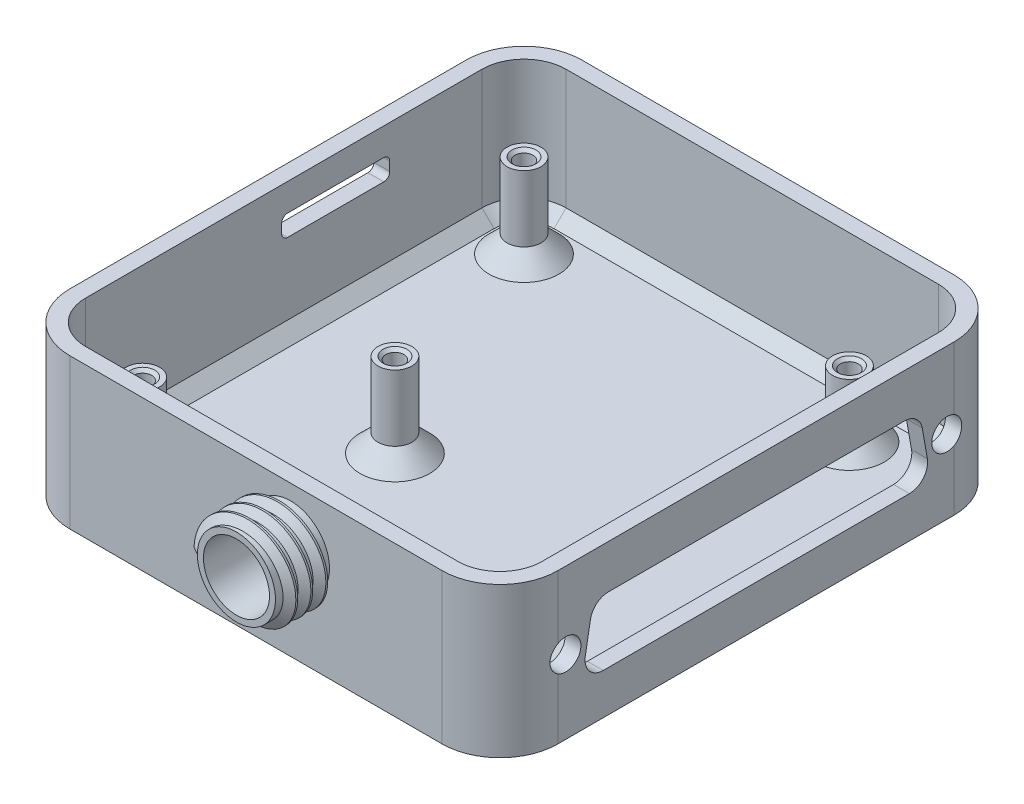
SolidWorks part; units mm, degrees
ref_plane "Front Plane" through (0, 0, 0) normal (0, 0, 1) x (1, 0, 0)
ref_plane "Top Plane" through (0, 0, 0) normal (0, 1, 0) x (1, 0, 0)
ref_plane "Right Plane" through (0, 0, 0) normal (1, 0, 0) x (0, 0, -1)
sketch "HRDAQ_PCB_Sketch" plane through (0, 0, 0) normal (0, 1, 0) x (1, 0, 0)
  line L0 (4, -38.85) -> (13, -38.85)
  line L1 (-27.1, -31.75) -> (27.1, -31.75) construction
  line L2 (-27.1, -31.75) -> (-27.1, 31.75) construction
  line L3 (-27.1, 31.75) -> (27.1, 31.75) construction
  line L4 (27.1, -31.75) -> (27.1, 31.75) construction
  line L5 (-27.1, -31.75) -> (27.1, 31.75) construction
  line L6 (-27.1, 31.75) -> (27.1, -31.75) construction
  line L7 (-28.25, 35.9) -> (33.75, 35.9)
  line L8 (-31.25, 32.9) -> (-31.25, -33.1)
  line L9 (-28.25, -36.1) -> (1.25, -36.1)
  line L10 (36.75, 32.9) -> (36.75, -33.1)
  line L11 (4, -38.85) -> (1.25, -36.1)
  line L12 (13, -38.85) -> (15.75, -36.1)
  line L13 (15.75, -36.1) -> (33.75, -36.1)
  circle A0 centre (-27.1, 31.75) radius 1.5
  circle A1 centre (27.1, 31.75) radius 1.5
  circle A2 centre (27.1, -31.75) radius 1.5
  circle A3 centre (-27.1, -31.75) radius 1.5
  circle A4 centre (-9.1, -7.75) radius 1.5
  arc A5 (-28.25, -36.1) -> (-31.25, -33.1) centre (-28.25, -33.1) cw
  arc A6 (33.75, -36.1) -> (36.75, -33.1) centre (33.75, -33.1) ccw
  arc A7 (36.75, 32.9) -> (33.75, 35.9) centre (33.75, 32.9) ccw
  arc A8 (-28.25, 35.9) -> (-31.25, 32.9) centre (-28.25, 32.9) ccw
  point P0 (0, 0)
  point P12 (8.5, -38.85)
  point P20 (8.5, -38.85)
  point P26 (36.75, -36.1)
  point P29 (36.75, 35.9)
  point P32 (-31.25, 35.9)
  dimension "D3" = 3
  dimension "D14" = 3
  dimension "D1" = 54.2
  dimension "D2" = 63.5
  dimension "D4" = 24
  dimension "D5" = 18
  dimension "D6" = 35.6
  dimension "D7" = 7.1
  dimension "D8" = 4.15
  dimension "D9" = 9
  dimension "D10" = 4.15
  dimension "D11" = 72
  dimension "D12" = 68
  dimension "D13" = 135
sketch "HRDAQ_PCB_Base_Sketch" plane through (0, 0, 0) normal (0, 1, 0) x (1, 0, 0)
  line L8 (-28.25, -40.1) -> (33.75, -40.1)
  line L9 (-37.89, 32.9) -> (-37.89, -33.1)
  line L10 (-28.25, -42.74) -> (33.75, -42.74)
  line L11 (43.39, -33.1) -> (43.39, 32.9)
  line L12 (33.75, 42.54) -> (-28.25, 42.54)
  line L16 (-35.25, 32.9) -> (-35.25, -33.1)
  line L17 (-28.25, -40.1) -> (-0.4069, -40.1)
  line L18 (-0.4069, -40.1) -> (2.3431, -42.85)
  line L19 (2.3431, -42.85) -> (14.6569, -42.85)
  line L20 (14.6569, -42.85) -> (17.4069, -40.1)
  line L21 (17.4069, -40.1) -> (33.75, -40.1)
  line L22 (40.75, -33.1) -> (40.75, 32.9)
  line L23 (33.75, 39.9) -> (-28.25, 39.9)
  line L24 (-35.25, 32.9) -> (-35.25, -33.1)
  line L30 (40.75, -33.1) -> (40.75, 32.9)
  line L31 (33.75, 39.9) -> (-28.25, 39.9)
  arc A4 (-37.89, -33.1) -> (-28.25, -42.74) centre (-28.25, -33.1) ccw
  arc A5 (33.75, -42.74) -> (43.39, -33.1) centre (33.75, -33.1) ccw
  arc A6 (43.39, 32.9) -> (33.75, 42.54) centre (33.75, 32.9) ccw
  arc A7 (-28.25, 42.54) -> (-37.89, 32.9) centre (-28.25, 32.9) ccw
  arc A8 (-35.25, -33.1) -> (-28.25, -40.1) centre (-28.25, -33.1) ccw
  arc A9 (33.75, -40.1) -> (40.75, -33.1) centre (33.75, -33.1) ccw
  arc A10 (40.75, 32.9) -> (33.75, 39.9) centre (33.75, 32.9) ccw
  arc A11 (-28.25, 39.9) -> (-35.25, 32.9) centre (-28.25, 32.9) ccw
  arc A12 (-35.25, -33.1) -> (-28.25, -40.1) centre (-28.25, -33.1) ccw
  arc A13 (33.75, -40.1) -> (40.75, -33.1) centre (33.75, -33.1) ccw
  arc A14 (40.75, 32.9) -> (33.75, 39.9) centre (33.75, 32.9) ccw
  arc A15 (-28.25, 39.9) -> (-35.25, 32.9) centre (-28.25, 32.9) ccw
  dimension "D1" = 4
  dimension "D2" = 2.64
sketch "Sketch1" plane through (0, 0, 0) normal (0, 1, 0) x (1, 0, 0)
  line L0 (-28.25, -42.74) -> (33.75, -42.74) construction
  line L1 (43.39, -33.1) -> (43.39, 32.9) construction
  line L2 (33.75, 42.54) -> (-28.25, 42.54) construction
  line L3 (-37.89, 32.9) -> (-37.89, -33.1) construction
  line L4 (-28.25, -42.74) -> (33.75, -42.74)
  line L5 (43.39, -33.1) -> (43.39, 32.9)
  line L6 (33.75, 42.54) -> (-28.25, 42.54)
  line L7 (-37.89, 32.9) -> (-37.89, -33.1)
  arc A0 (-37.89, -33.1) -> (-28.25, -42.74) centre (-28.25, -33.1) ccw construction
  arc A1 (33.75, -42.74) -> (43.39, -33.1) centre (33.75, -33.1) ccw construction
  arc A2 (43.39, 32.9) -> (33.75, 42.54) centre (33.75, 32.9) ccw construction
  arc A3 (-28.25, 42.54) -> (-37.89, 32.9) centre (-28.25, 32.9) ccw construction
  arc A4 (-37.89, -33.1) -> (-28.25, -42.74) centre (-28.25, -33.1) ccw
  arc A5 (33.75, -42.74) -> (43.39, -33.1) centre (33.75, -33.1) ccw
  arc A6 (43.39, 32.9) -> (33.75, 42.54) centre (33.75, 32.9) ccw
  arc A7 (-28.25, 42.54) -> (-37.89, 32.9) centre (-28.25, 32.9) ccw
  circle A8 centre (27.1, -31.75) radius 1.5 construction
  circle A9 centre (-27.1, -31.75) radius 1.5 construction
  circle A10 centre (-9.1, -7.75) radius 1.5 construction
  circle A11 centre (27.1, 31.75) radius 1.5 construction
  circle A12 centre (-27.1, 31.75) radius 1.5 construction
  circle A13 centre (27.1, -31.75) radius 1.5
  circle A14 centre (-27.1, -31.75) radius 1.5
  circle A15 centre (-9.1, -7.75) radius 1.5
  circle A16 centre (27.1, 31.75) radius 1.5
  circle A17 centre (-27.1, 31.75) radius 1.5
extrude "Base_Extrude" add sketch "Sketch1" along normal blind 3
extrude "Wall_Extrude" add sketch "HRDAQ_PCB_Base_Sketch" along normal blind 25
chamfer "Base_Chamfer" distance 2 angle 45 8 edges at (2.75, 3, 40.1) (-33.1997, 3, 38.0497) (38.6997, 3, 38.0497) (-35.25, 3, 0.1) (40.75, 3, 0.1) (-33.1997, 3, -37.8497) (38.6997, 3, -37.8497) (2.75, 3, -39.9)
sketch "Sketch2" plane through (0, 3, 0) normal (0, 1, 0) x (1, 0, 0)
  circle A0 centre (-27.1, 31.75) radius 2.82
  circle A1 centre (-9.1, -7.75) radius 2.82
  circle A2 centre (-27.1, -31.75) radius 2.82
  circle A3 centre (-27.1, 31.75) radius 1.5
  circle A4 centre (-9.1, -7.75) radius 1.5
  circle A5 centre (-27.1, -31.75) radius 1.5
  circle A7 centre (-27.1, 31.75) radius 1.5 construction
  dimension "D1" = 5.64
extrude "Small_Peg_Extrude" add sketch "Sketch2" along normal blind 14
sketch "Sketch3" plane through (0, 3, 0) normal (0, 1, 0) x (1, 0, 0)
  circle A0 centre (27.1, 31.75) radius 2.82
  circle A1 centre (27.1, -31.75) radius 2.82
  circle A2 centre (27.1, 31.75) radius 1.5
  circle A3 centre (27.1, -31.75) radius 1.5
  circle A4 centre (27.1, 31.75) radius 1.5 construction
  dimension "D1" = 5.64
extrude "DSUB_Peg_Extrude" add sketch "Sketch3" along normal blind 11
chamfer "Peg_Chamfer_1" distance 3 angle 45 5 edges at (27.1, 3, 34.57) (-27.1, 3, 34.57) (-9.1, 3, 10.57) (27.1, 3, -28.93) (-27.1, 3, -28.93)
chamfer "Peg_Chamfer_2" distance 0.5 angle 45 5 edges at (27.1, 14, 33.25) (-27.1, 17, 33.25) (-9.1, 17, 9.25) (27.1, 14, -30.25) (-27.1, 17, -30.25)
ref_plane "HRDAQ_PCB_Top_Plane" through (0, 18.55, 0) normal (0, 1, 0) x (1, 0, 0)
sketch "Sketch4" plane through (0, 0, 42.74) normal (0, 0, 1) x (1, 0, 0)
  line L0 (8.5, 0) -> (8.5, 25) construction
  line L1 (-28.25, 25) -> (33.75, 25) construction
  line L2 (50.856, 18.55) -> (-50.856, 18.55) construction
  circle A0 centre (8.5, 15.95) radius 2.6 construction
  circle A1 centre (8.5, 15.95) radius 5.5
  point P0 (8.5, 0)
  dimension "D1" = 5.2
  dimension "D2" = 11
extrude "SMA_Cut_Extrude" cut sketch "Sketch4" against normal up to surface (2.64 mm away) up to face at (2.75, 15, 40.1)
sketch "Sketch5" plane through (43.39, 0, 0) normal (1, 0, 0) x (0, 0, -1)
  line L0 (0, 0) -> (-0.1, 25) construction
  line L1 (-33.1, 25) -> (32.9, 25) construction
  line L2 (50.856, 18.55) -> (-50.856, 18.55) construction
  line L3 (-34.7074, 6.0024) -> (34.6092, 6.0024)
  line L4 (-34.7074, 6.0024) -> (-34.7074, 18.55)
  line L5 (-34.7074, 18.55) -> (34.6092, 18.55)
  line L6 (34.6092, 6.0024) -> (34.6092, 18.55)
  line L7 (-34.7074, 6.0024) -> (34.6092, 18.55) construction
  line L8 (-34.7074, 18.55) -> (34.6092, 6.0024) construction
  line L9 (-34.7074, 12.2762) -> (34.6092, 12.2762) construction
  line L10 (-25.5468, 7.8265) -> (25.4499, 7.8265)
  line L12 (-26.3992, 16.7259) -> (26.3062, 16.7259)
  line L14 (-27.9684, 7.8265) -> (27.8702, 16.7259) construction
  line L15 (-27.9684, 16.7259) -> (27.8702, 7.8265) construction
  line L16 (-31.7991, 12.2762) -> (31.7009, 12.2762) construction
  line L17 (-27.5479, 10.2114) -> (-26.6953, 15.0468)
  line L18 (27.4513, 10.2102) -> (26.6015, 15.0456)
  line L19 (-27.9684, 7.8265) -> (27.8702, 7.8265)
  line L20 (-24.6942, 16.7259) -> (24.6001, 16.7259)
  line L21 (-26.3992, 16.7259) -> (-27.9684, 16.7259)
  line L22 (-27.9684, 16.7259) -> (-27.9684, 7.8265)
  line L23 (27.8702, 7.8265) -> (27.8702, 16.7259)
  line L24 (27.8702, 16.7259) -> (26.3062, 16.7259)
  circle A2 centre (-31.7991, 12.2762) radius 2.54
  circle A3 centre (31.7009, 12.2762) radius 2.54
  arc A4 (25.4499, 7.8265) -> (27.4513, 10.2102) centre (25.4499, 9.8585) ccw
  arc A5 (26.6015, 15.0456) -> (24.6001, 16.7259) centre (24.6001, 14.6939) ccw
  arc A6 (-26.6953, 15.0468) -> (-24.6942, 16.7259) centre (-24.6942, 14.6939) cw
  arc A7 (-25.5468, 7.8265) -> (-27.5479, 10.2114) centre (-25.5468, 9.8585) cw
  point P5 (-0.0491, 12.2762)
  point P12 (-0.0491, 12.2762)
  point P23 (-0.0491, 12.2762)
  line M3 (32.9, 0) -> (32.9, 25)
  line M5 (-33.1, 25) -> (-33.1, 0)
  dimension "D6" = 63.5
  dimension "D5" = 5.08
  dimension "D7" = 2.032
  dimension "D1" = 69.3166
  dimension "D2" = 12.5476
  dimension "D3" = 55.8386
  dimension "D4" = 8.8994
extrude "DSUB_Cut_Extrude" cut sketch "Sketch5" against normal up to vertex (9.64 mm away) contours A7 L10 A4 L18 A5 L12 A6 L17 | A2 M5 | A2 M5 | A3 M3 | A3 M3 region at (43.39, 12.2762, 31.3781) region at (43.39, 12.2762, 33.6077) region at (43.39, 12.2762, -33.4507) region at (43.39, 12.2762, -31.2329) region at (43.39, 12.2446, 0.0478) up to point (33.75, 25, -39.9)
sketch "Sketch6" plane through (-37.89, 0, 0) normal (-1, 0, 0) x (0, 0, 1)
  line L0 (50.856, 18.55) -> (-50.856, 18.55) construction
  line L1 (-16.54, 20.43) -> (-0.54, 20.43)
  line L2 (-17.54, 19.43) -> (-17.54, 17.93)
  line L3 (-16.54, 16.93) -> (-0.54, 16.93)
  line L4 (0.46, 19.43) -> (0.46, 17.93)
  line L5 (-42.54, 25) -> (-42.54, 0) construction
  arc A0 (-17.54, 17.93) -> (-16.54, 16.93) centre (-16.54, 17.93) ccw
  arc A1 (-0.54, 16.93) -> (0.46, 17.93) centre (-0.54, 17.93) ccw
  arc A2 (-0.54, 20.43) -> (0.46, 19.43) centre (-0.54, 19.43) cw
  arc A3 (-16.54, 20.43) -> (-17.54, 19.43) centre (-16.54, 19.43) ccw
  point P10 (-17.54, 16.93)
  point P13 (0.46, 16.93)
  point P16 (0.46, 20.43)
  point P19 (-17.54, 20.43)
  dimension "D5" = 1
  dimension "D1" = 1.62
  dimension "D2" = 3.5
  dimension "D3" = 18
  dimension "D4" = 25
extrude "SD-Card_Cut_Extrude" cut sketch "Sketch6" against normal up to surface (2.64 mm away) up to face at (-35.25, 15, 0.1)
sketch "Sketch7" plane through (43.39, 0, 0) normal (1, 0, 0) x (0, 0, -1)
  line L0 (-27.5479, 10.2114) -> (-26.6953, 15.0468) construction
  line L1 (-25.5468, 7.8265) -> (25.4499, 7.8265) construction
  line L2 (27.4513, 10.2102) -> (26.6015, 15.0456) construction
  line L3 (-24.6942, 16.7259) -> (24.6001, 16.7259) construction
  line L4 (-27.5479, 10.2114) -> (-26.6953, 15.0468)
  line L5 (-25.5468, 7.8265) -> (25.4499, 7.8265)
  line L6 (27.4513, 10.2102) -> (26.6015, 15.0456)
  line L7 (-24.6942, 16.7259) -> (24.6001, 16.7259)
  line L8 (-24.6942, 17.7259) -> (24.6001, 17.7259)
  line L9 (28.4362, 10.3833) -> (27.5864, 15.2187)
  line L10 (-25.5468, 6.8265) -> (25.4499, 6.8265)
  line L11 (-28.5327, 10.385) -> (-27.6801, 15.2204)
  arc A0 (-24.6942, 16.7259) -> (-26.6953, 15.0468) centre (-24.6942, 14.6939) ccw construction
  arc A1 (-27.5479, 10.2114) -> (-25.5468, 7.8265) centre (-25.5468, 9.8585) ccw construction
  arc A2 (25.4499, 7.8265) -> (27.4513, 10.2102) centre (25.4499, 9.8585) ccw construction
  arc A3 (26.6015, 15.0456) -> (24.6001, 16.7259) centre (24.6001, 14.6939) ccw construction
  arc A4 (-24.6942, 16.7259) -> (-26.6953, 15.0468) centre (-24.6942, 14.6939) ccw
  arc A5 (-27.5479, 10.2114) -> (-25.5468, 7.8265) centre (-25.5468, 9.8585) ccw
  arc A6 (25.4499, 7.8265) -> (27.4513, 10.2102) centre (25.4499, 9.8585) ccw
  arc A7 (26.6015, 15.0456) -> (24.6001, 16.7259) centre (24.6001, 14.6939) ccw
  arc A8 (27.5864, 15.2187) -> (24.6001, 17.7259) centre (24.6001, 14.6939) ccw
  arc A9 (25.4499, 6.8265) -> (28.4362, 10.3833) centre (25.4499, 9.8585) ccw
  arc A10 (-28.5327, 10.385) -> (-25.5468, 6.8265) centre (-25.5468, 9.8585) ccw
  arc A11 (-24.6942, 17.7259) -> (-27.6801, 15.2204) centre (-24.6942, 14.6939) ccw
  dimension "D1" = 1
extrude "DSUB_OFFSET_Cut_Exrude" cut sketch "Sketch7" against normal up to surface (2.64 mm away) up to face at (40.75, 13.6381, 0.0873)
sketch "Sketch8" plane through (0, 0, 42.74) normal (0, 0, 1) x (1, 0, 0)
  circle A0 centre (8.5, 15.95) radius 6.5
  circle A1 centre (8.5, 15.95) radius 5.5 construction
  circle A2 centre (8.5, 15.95) radius 5.5
  dimension "D1" = 1
extrude "SMA_Cover_Extrude" add sketch "Sketch8" along normal blind 9
thread "SMA_Cover_Thread" pitch 2.5 method extrude profile "Thread Profile1" start angle 0, offset 0, length 0, pitch 2.5, diameter 13
ref_plane "Plane1" through (2, 15.95, 51.74) normal (0, -1, 0) x (-1, 0, 0)
sketch "Thread Profile1" plane through (2, 15.95, 51.74) normal (0, -1, 0) x (-1, 0, 0)
  line L0 (0, 0) -> (0, 2.5) construction
  line L1 (0, 0) -> (1.3532, 0.7812)
  line L2 (1.3532, 0.7812) -> (1.3532, 1.0937)
  line L3 (1.3532, 1.0937) -> (0, 1.875)
  line L4 (1.3532, 0.9375) -> (0, 0.9375) construction
  line L11 (0, 0) -> (0, 1.875)
  point P2 (0, 0)
  dimension "Pitch" = 2.5
  dimension "Profile_Angle" = 60
  dimension "Profile_Land" = 0.3125
  dimension "Profile_Height" = 1.3532
fillet "SMA_Cover_Fillet" radius 2 1 edges at (3, 15.95, 40.1)
equation "\"Wall_Thickness\"= 2.64mm"
equation "\"D2@HRDAQ_PCB_Base_Sketch\" = \"Wall_Thickness\""
equation "\"Base_Thickness\"= 3mm"
equation "\"D1@Base_Extrude\" = \"Base_Thickness\""
equation "\"Wall_Height\" = 22mm"
equation "\"D1@Wall_Extrude\" = \"Base_Thickness\" + \"Wall_Height\""
equation "\"Small_Peg_Height\"= 14mm"
equation "\"D1@Small_Peg_Extrude\" = \"Small_Peg_Height\""
equation "\"DSUB_Peg_Offset\"= 3mm"
equation "\"D1@DSUB_Peg_Extrude\" = \"Small_Peg_Height\" - \"DSUB_Peg_Offset\""
equation "\"SMA_Hole_Diameter\"= 11mm"
equation "\"D2@Sketch4\"=\"SMA_Hole_Diameter\""
